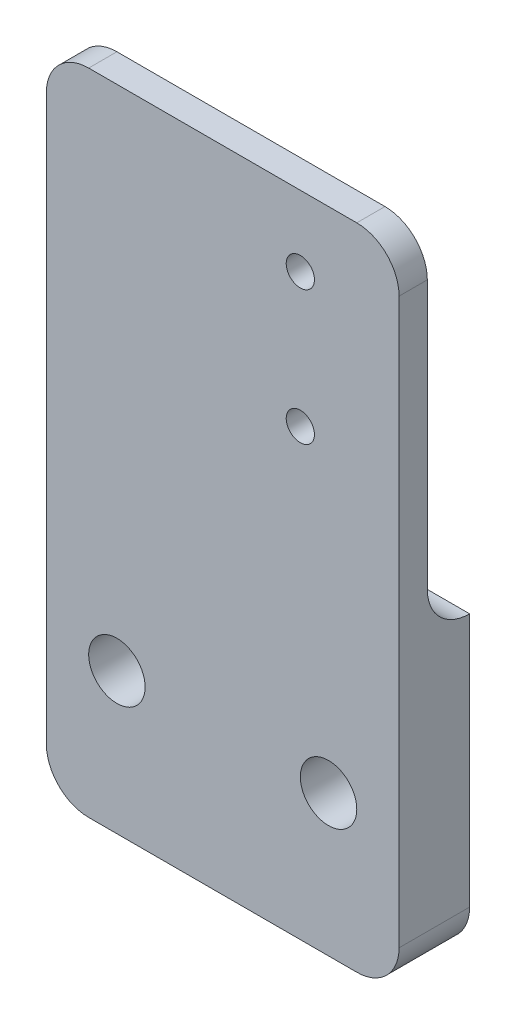
SolidWorks part; units mm, degrees
ref_plane "正面" through (0, 0, 0) normal (0, 0, 1) x (1, 0, 0)
ref_plane "平面" through (0, 0, 0) normal (0, 1, 0) x (1, 0, 0)
ref_plane "右側面" through (0, 0, 0) normal (1, 0, 0) x (0, 0, -1)
sketch "ｽｹｯﾁ1" plane through (0, 0, 0) normal (0, 0, 1) x (1, 0, 0)
  line L1 (0, 0) -> (25, 0)
  line L2 (0, 0) -> (0, 46)
  line L3 (0, 46) -> (25, 46)
  line L4 (25, 0) -> (25, 46)
  dimension "D1" = 46
  dimension "D2" = 25
extrude "ﾎﾞｽ - 押し出し1" add sketch "ｽｹｯﾁ1" along normal blind 5
sketch "ｽｹｯﾁ2" plane through (0, 0, 0) normal (0, 0, -1) x (-1, 0, 0)
  line L0 (-25, 0) -> (-25, 46) construction
  line L1 (0, 46) -> (-25, 46)
  line L2 (0, 46) -> (0, 21)
  line L3 (0, 21) -> (-25, 21)
  line L4 (-25, 46) -> (-25, 21)
  dimension "D1" = 25
  dimension "D2" = 25
extrude "ｶｯﾄ - 押し出し1" cut sketch "ｽｹｯﾁ2" against normal blind 3
sketch "ｽｹｯﾁ3" plane through (0, 0, 5) normal (0, 0, 1) x (1, 0, 0)
  line L0 (0, 0) -> (25, 0) construction
  line L1 (0, 46) -> (0, 0) construction
  line L2 (25, 0) -> (25, 46) construction
  point P0 (5, 10)
  point P1 (20, 10)
  dimension "D1" = 10
  dimension "D2" = 10
  dimension "D3" = 5
  dimension "D4" = 5
hole_wizard "M4x0.7 ねじ穴1" positions "ｽｹｯﾁ4" profile "ｽｹｯﾁ5" tap size "M4x0.7" standard "JIS" end condition up to next
sketch "ｽｹｯﾁ4" plane through (0, 0, 5) normal (0, 0, 1) x (1, 0, 0)
  point P0 (5, 10)
  point P3 (20, 10)
sketch "ｽｹｯﾁ5" plane through (5, 10, 5) normal (1, 0, 0) x (0, -1, 0)
  line L0 (0, 0) -> (0, 5)
  line L1 (0, 5) -> (2, 5)
  line L2 (2, 5) -> (2, 0)
  line L5 (2, 0) -> (0, 0)
  line L11 (0, -6.35) -> (0, 107.95) construction
  dimension "ねじ山の主要直径" = 4
  dimension "次ｻｰﾌｪｽまでのねじ下穴ﾄﾞﾘﾙの深さ" = 5
sketch "ｽｹｯﾁ6" plane through (0, 0, 5) normal (0, 0, 1) x (1, 0, 0)
  line L0 (25, 0) -> (25, 46) construction
  line L1 (25, 46) -> (0, 46) construction
  point P0 (18, 41)
  point P1 (18, 31.5)
  dimension "D1" = 7
  dimension "D2" = 7
  dimension "D3" = 5
  dimension "D4" = 9.5
hole_wizard "M2x0.4 ねじ穴1" positions "ｽｹｯﾁ7" profile "ｽｹｯﾁ8" tap size "M2x0.4" standard "JIS" end condition up to next
sketch "ｽｹｯﾁ7" plane through (0, 0, 5) normal (0, 0, 1) x (1, 0, 0)
  point P0 (18, 41)
  point P3 (18, 31.5)
sketch "ｽｹｯﾁ8" plane through (18, 41, 5) normal (1, 0, 0) x (0, -1, 0)
  line L0 (0, 0) -> (0, 2)
  line L1 (0, 2) -> (1, 2)
  line L2 (1, 2) -> (1, 0)
  line L5 (1, 0) -> (0, 0)
  line L11 (0, -6.35) -> (0, 107.95) construction
  dimension "ねじ山の主要直径" = 2
  dimension "次ｻｰﾌｪｽまでのねじ下穴ﾄﾞﾘﾙの深さ" = 2
fillet "ﾌｨﾚｯﾄ1" radius 3 1 edges at (12.5, 21, 3)
fillet "ﾌｨﾚｯﾄ2" radius 3 4 edges at (0, 46, 4) (25, 46, 4) (0, 0, 2.5) (25, 0, 2.5)
